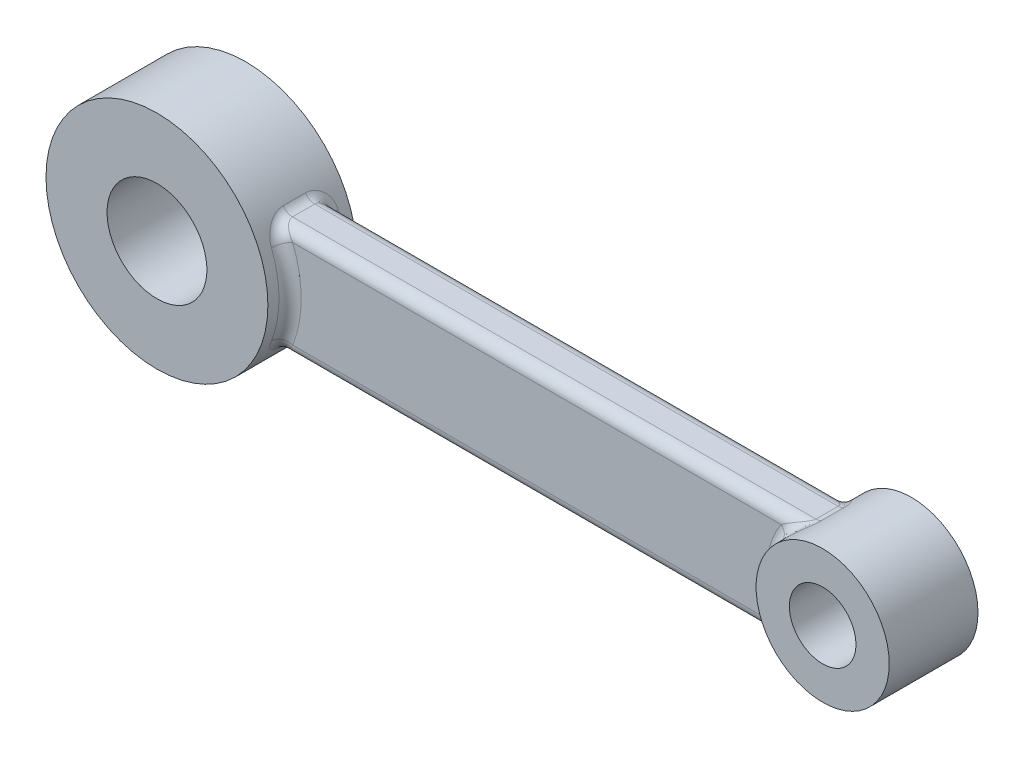
SolidWorks part; units mm, degrees
ref_plane "Front Plane" through (0, 0, 0) normal (0, 0, 1) x (1, 0, 0)
ref_plane "Top Plane" through (0, 0, 0) normal (0, 1, 0) x (1, 0, 0)
ref_plane "Right Plane" through (0, 0, 0) normal (1, 0, 0) x (0, 0, -1)
sketch "Sketch1" plane through (0, 0, 0) normal (0, 0, 1) x (1, 0, 0)
  line L1 (-15, -2.5) -> (15, -2.5)
  line L2 (-15, -2.5) -> (-15, 2.5)
  line L3 (-15, 2.5) -> (15, 2.5)
  line L4 (15, -2.5) -> (15, 2.5)
  line L5 (-15, -2.5) -> (15, 2.5) construction
  line L6 (-15, 2.5) -> (15, -2.5) construction
  point P0 (0, 0)
  dimension "D1" = 30
  dimension "D2" = 5
extrude "Boss-Extrude1" add sketch "Sketch1" along normal mid plane 2
sketch "Sketch3" plane through (0, 0, 0) normal (0, 0, 1) x (1, 0, 0)
  line L0 (15, -2.5) -> (15, 2.5) construction
  line L1 (-15, 2.5) -> (-15, -2.5) construction
  circle A0 centre (15, 0) radius 3
  circle A1 centre (-15, 0) radius 5
  dimension "D1" = 6
  dimension "D2" = 10
extrude "Boss-Extrude3" add sketch "Sketch3" along normal mid plane 4
sketch "Sketch4" plane through (0, 0, -2) normal (0, 0, -1) x (-1, 0, 0)
  line L0 (-15, 3) -> (-15, -3) construction
  line L1 (15, 5) -> (15, -5) construction
  line L2 (-18, 0) -> (-12, 0) construction
  line L4 (10, 0) -> (20, 0) construction
  circle A0 centre (-15, 0) radius 3 construction
  circle A1 centre (-15, 0) radius 1.5
  circle A2 centre (15, 0) radius 5 construction
  arc A3 (10.6699, 2.5) -> (10.6699, -2.5) centre (15, 0) ccw construction
  circle A4 centre (15, 0) radius 2.25
  dimension "D1" = 3
  dimension "D2" = 4.5
extrude "Cut-Extrude1" cut sketch "Sketch4" against normal through all
fillet "Fillet1" radius 0.5 4 edges at (1.3359, 2.5, -1) (1.3359, 2.5, 1) (1.3359, -2.5, 1) (1.3359, -2.5, -1)
fillet "Fillet2" radius 0.5 16 edges at (-10.5801, -2.3376, -0.8688) (-10.6699, -2.5, 0) (-10.6204, -2.4123, 0.7829) (-10, 0, 1) (-10.5801, 2.3376, 0.8688) (-10.6699, 2.5, 0) (-10.6204, 2.4123, -0.7829) (13.1981, 2.3986, -0.8019) (13.3417, 2.5, 0) (13.2762, 2.4553, 0.7066) (12, 0, 1) (13.1981, -2.3986, 0.8019) (13.3417, -2.5, 0) (13.2762, -2.4553, -0.7066) (-10, 0, -1) (12, 0, -1)
